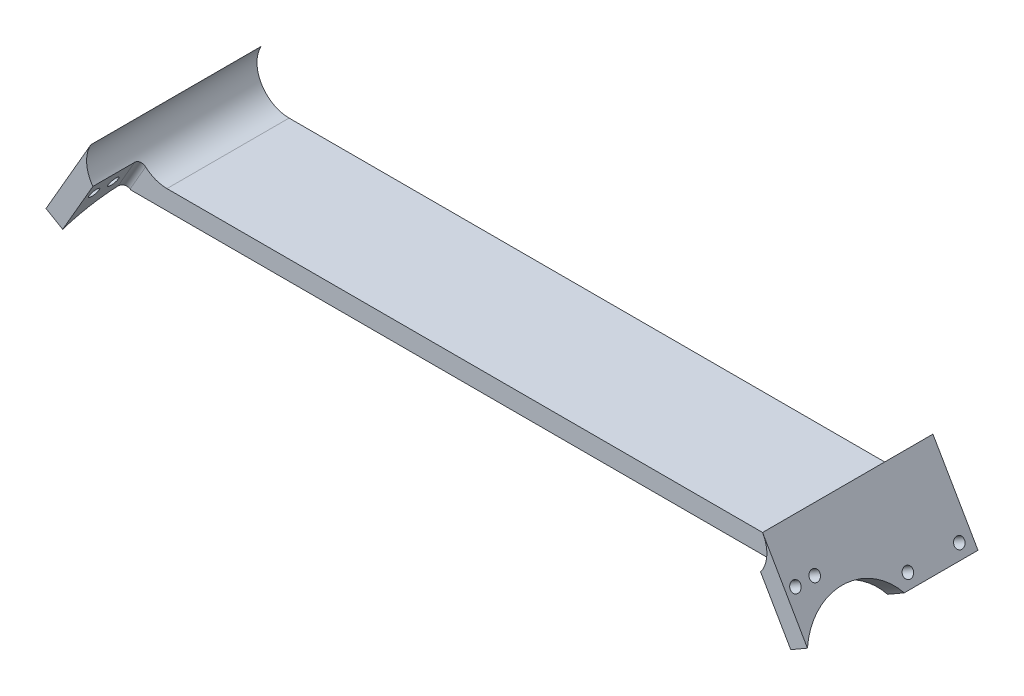
SolidWorks part; units mm, degrees
material "Nylon 101 40%"
ref_plane "Front Plane" through (0, 0, 0) normal (0, 0, 1) x (1, 0, 0)
ref_plane "Top Plane" through (0, 0, 0) normal (0, 1, 0) x (1, 0, 0)
ref_plane "Right Plane" through (0, 0, 0) normal (1, 0, 0) x (0, 0, -1)
sketch "Sketch2" plane through (0, 0, 0) normal (0, 0, 1) x (1, 0, 0)
  line L1 (-113.1402, 0) -> (113.1402, 0)
  line L3 (-118.5051, -9.2924) -> (-113.1402, 0)
  line L5 (118.5051, -9.2924) -> (113.1402, 0)
  line L7 (113.309, -12.2924) -> (118.5051, -9.2924)
  line L9 (-118.5051, -9.2924) -> (-113.309, -12.2924)
  line L10 (-109.6761, -6) -> (109.6761, -6)
  line L11 (113.309, -12.2924) -> (109.6761, -6)
  line L13 (0, 0) -> (0, -6) construction
  line L14 (-113.309, -12.2924) -> (-109.6761, -6)
  dimension "D1" = 6
  dimension "D2" = 226.2804
  dimension "D3" = 120
  dimension "D4" = 10.7299
extrude "Boss-Extrude1" add sketch "Sketch2" along normal blind 2
sketch "Sketch5" plane through (84.8551, 48.9911, 0) normal (0.866, 0.5, 0) x (0, 0, -1)
  line L0 (-38, -58.7) -> (-38, -20.3321) construction
  line L1 (-38, -58.7) -> (-38, -20.3321) construction
  arc A0 (-22.9322, -67.3) -> (-22.9322, -85.1) centre (-38, -76.2) ccw construction
  arc A2 (-22.9322, -67.3) -> (-22.9322, -85.1) centre (-38, -76.2) ccw
extrude "Boss-Extrude2" add sketch "Sketch2<3>" along normal up to surface (38 mm away)
sketch "Sketch2<3>" plane through (0, 0, 0) normal (0, 0, 1) x (1, 0, 0) same geometry as "Sketch2"
sketch "Sketch6" plane through (0, 0, 0) normal (0, 0, -1) x (-1, 0, 0)
  line L0 (-118.5051, -9.2924) -> (-113.1402, 0) construction
  line L1 (-114.8722, -3) -> (-104.4799, 15)
  line L2 (118.5051, -9.2924) -> (113.1402, 0) construction
  line L3 (114.8722, -3) -> (104.4799, 15)
  line L4 (109.6761, -6) -> (-109.6761, -6) construction
  line L5 (113.1402, 0) -> (-113.1402, 0) construction
  line L6 (95.8197, 0) -> (-95.8197, 0)
  line L7 (109.6761, -6) -> (-109.6761, -6)
  line L14 (-113.309, -12.2924) -> (-109.6761, -6) construction
  line L15 (-113.309, -12.2924) -> (-109.6761, -6) construction
  line L16 (-109.6761, -6) -> (-114.8722, -3)
  line L17 (113.309, -12.2924) -> (109.6761, -6) construction
  line L18 (113.309, -12.2924) -> (109.6761, -6) construction
  line L19 (109.6761, -6) -> (114.8722, -3)
  arc A0 (95.8197, 0) -> (104.4799, 15) centre (95.8197, 10) ccw
  arc A1 (-104.4799, 15) -> (-95.8197, 0) centre (-95.8197, 10) ccw
  dimension "D2" = 20
extrude "Manual fillet" add sketch "Sketch6" against normal up to surface (38 mm away) up to face at (0, -6.8962, 38)
sketch "Sketch7" plane through (0, 0, 0) normal (0, 0, 1) x (1, 0, 0)
  line L0 (0, 0) -> (0, -6) construction
  line L1 (-109.6761, -6) -> (109.6761, -6) construction
  line L2 (0, -3) -> (-114.8722, -3) construction
  line L3 (-104.4799, 15) -> (-118.5051, -9.2924) construction
  line L4 (0, -3) -> (114.8722, -3) construction
  line L5 (118.5051, -9.2924) -> (104.4799, 15) construction
  line L6 (57.4361, -3) -> (57.4361, -6) construction
  line L7 (-57.4361, -3) -> (-57.4361, -6) construction
  line L8 (57.4361, -4.5) -> (0, -4.5) construction
  line L9 (-57.4361, -4.5) -> (0, -4.5) construction
  line L10 (-28.7181, -4.5) -> (-28.7181, 0) construction
  line L11 (95.8197, 0) -> (-95.8197, 0) construction
  line L12 (28.7181, -4.5) -> (28.7181, 0) construction
  line L13 (114.8722, -3) -> (114.8722, -15) construction
  line L14 (109.6761, -6) -> (113.309, -12.2924) construction
  line L15 (-114.8722, -3) -> (-114.8722, -15) construction
  line L16 (-113.309, -12.2924) -> (-109.6761, -6) construction
  line L17 (-57.4361, -4.5) -> (-114.8722, -4.5) construction
  line L18 (-86.1542, -4.5) -> (-86.1542, 0) construction
  line L19 (57.4361, -4.5) -> (114.8722, -4.5) construction
  line L20 (86.1542, -4.5) -> (86.1542, -3) construction
  circle A0 centre (57.4361, -3) radius 1.4
  circle A1 centre (0, -3) radius 1.4
  circle A2 centre (-57.4361, -3) radius 1.4
  circle A3 centre (-28.7181, -3) radius 1.4
  circle A4 centre (28.7181, -3) radius 1.4
  circle A5 centre (-86.1542, -3) radius 1.4
  circle A6 centre (86.1542, -3) radius 1.4
  circle A7 centre (-86.1542, -3) radius 1.6 construction
  circle A8 centre (-57.4361, -3) radius 1.6 construction
  circle A9 centre (-28.7181, -3) radius 1.6 construction
  circle A10 centre (0, -3) radius 1.6 construction
  circle A11 centre (28.7181, -3) radius 1.6 construction
  circle A12 centre (57.4361, -3) radius 1.6 construction
  circle A13 centre (86.1542, -3) radius 1.6 construction
  point P26 (-28.7181, -3)
  point P27 (-28.7181, -3)
  point P32 (28.7181, -3)
  point P33 (28.7181, -3)
  point P45 (-86.1542, -3)
  point P46 (-86.1542, -3)
  dimension "D1" = 2.8
  dimension "D2" = 0.2
extrude "Bottom screws" cut sketch "Sketch7" along normal blind 9
sketch "Sketch8" plane through (-79.659, 45.9911, 0) normal (0.866, -0.5, 0) x (0, 0, -1)
  line L0 (0, -39.2496) -> (0, -67.3) construction
  line L5 (-5.6, -63.6671) -> (-38, -63.6671) construction
  line L6 (-38, -67.3) -> (-38, -60.0342) construction
  circle A1 centre (-20, -63.6671) radius 1.6
  circle A2 centre (-4, -63.6671) radius 1.6
  dimension "D1" = 3.2
  dimension "D3" = 20
  dimension "D2" = 4
extrude "Left screws" cut sketch "Sketch8" against normal up to next
sketch "Sketch9" plane through (79.659, 45.9911, 0) normal (-0.866, -0.5, 0) x (0, 0, 1)
  line L0 (0, -60.0342) -> (0, -67.3) construction
  line L5 (2.4, -63.6671) -> (38, -63.6671) construction
  line L6 (38, -60.0342) -> (38, -67.3) construction
  circle A0 centre (20, -63.6671) radius 1.6
  circle A2 centre (4, -63.6671) radius 1.6
  dimension "D1" = 3.2
  dimension "D2" = 4
  dimension "D3" = 20
extrude "Right screws" cut sketch "Sketch9" against normal up to next
sketch "Sketch12" plane through (0, 0, 38) normal (0, 0, 1) x (1, 0, 0)
  line L8 (-109.6761, -6) -> (109.6761, -6)
  line L9 (109.6761, -6) -> (113.309, -12.2924)
  line L10 (113.309, -12.2924) -> (118.5051, -9.2924)
  line L11 (118.5051, -9.2924) -> (104.4799, 15)
  line L12 (95.8197, 0) -> (-95.8197, 0)
  line L13 (-104.4799, 15) -> (-118.5051, -9.2924)
  line L14 (-118.5051, -9.2924) -> (-113.309, -12.2924)
  line L15 (-113.309, -12.2924) -> (-109.6761, -6)
  line L17 (103.8664, 4.0627) -> (113.309, -12.2924)
  line L18 (113.309, -12.2924) -> (118.5051, -9.2924)
  line L19 (118.5051, -9.2924) -> (104.4799, 15)
  line L21 (-104.4799, 15) -> (-118.5051, -9.2924)
  line L22 (-118.5051, -9.2924) -> (-113.309, -12.2924)
  line L23 (-113.309, -12.2924) -> (-103.8664, 4.0627)
  arc A2 (95.8197, 0) -> (104.4799, 15) centre (95.8197, 10) ccw
  arc A3 (-104.4799, 15) -> (-95.8197, 0) centre (-95.8197, 10) ccw
  arc A4 (103.8664, 4.0627) -> (104.4799, 15) centre (95.8197, 10) ccw
  arc A5 (-104.4799, 15) -> (-103.8664, 4.0627) centre (-95.8197, 10) ccw
  dimension "D1" = 0
extrude "Boss-Extrude3" add sketch "Sketch12" along normal blind 15
sketch "Sketch10" plane through (84.8551, 48.9911, 0) normal (0.866, 0.5, 0) x (0, 0, -1)
  line L0 (-38, -58.7) -> (-38, -20.3321) construction
  line L1 (-38, -93.7) -> (-38, -58.7) construction
  line L3 (-44, -53.7) -> (-38, -53.7) construction
  line L4 (-38, -76.2) -> (0, -76.2) construction
  line L5 (0, 65.2303) -> (0, 51.2051) construction
  line L6 (0, -76.2) -> (0, -67.3) construction
  line L7 (-20, -63.6671) -> (-38, -63.6671) construction
  line L9 (-44, -53.7) -> (-50, -53.7) construction
  line L10 (-38, -53.7) -> (-38, -58.7) construction
  circle A0 centre (-20, -63.6671) radius 1.6 construction
  circle A1 centre (-38, -76.2) radius 17.5
  circle A2 centre (-20, -63.6671) radius 1.6 construction
  circle A3 centre (-44, -53.7) radius 1.6
  circle A4 centre (-50, -53.7) radius 1.6
  dimension "D2" = 35
  dimension "D1" = 8.9
  dimension "D3" = 6
  dimension "D4" = 5
  dimension "D5" = 6
extrude "Cut-Extrude1" cut sketch "Sketch10" against normal up to next
sketch "Sketch11" plane through (-84.8551, 48.9911, 0) normal (-0.866, 0.5, 0) x (0, 0, 1)
  line L0 (38, -76.2) -> (38, -58.7) construction
  line L2 (0, -39.2496) -> (0, -67.3) construction
  line L3 (38, -76.2) -> (0, -76.2) construction
  line L4 (38, 46.7551) -> (0, 46.7551) construction
  line L5 (38, -58.7) -> (38, -53.7) construction
  line L6 (0, -76.2) -> (0, -67.3) construction
  line L7 (44, -53.7) -> (50, -53.7) construction
  line L9 (44, 58.0051) -> (50, 58.0051) construction
  line L11 (38, -53.7) -> (44, -53.7) construction
  line L12 (44, 58.0051) -> (38, 58.0051) construction
  circle A0 centre (38, -76.2) radius 17.5
  circle A1 centre (50, -53.7) radius 1.6
  circle A2 centre (44, -53.7) radius 1.6
  circle A3 centre (20, -63.6671) radius 1.6 construction
  dimension "D2" = 35
  dimension "D1" = 8.9
  dimension "D3" = 5
extrude "Cut-Extrude2" cut sketch "Sketch11" against normal up to next
fillet "Fillet1" radius 2 2 edges at (106.4377, -0.3909, 38) (-106.4377, -0.3909, 38)
equation "\"D1@Sketch11\" = \"D1@Sketch10\""
equation "\"D2@Sketch11\" = \"D2@Sketch10\""
equation "\"D3@Sketch11\"= \"D4@Sketch10\""
